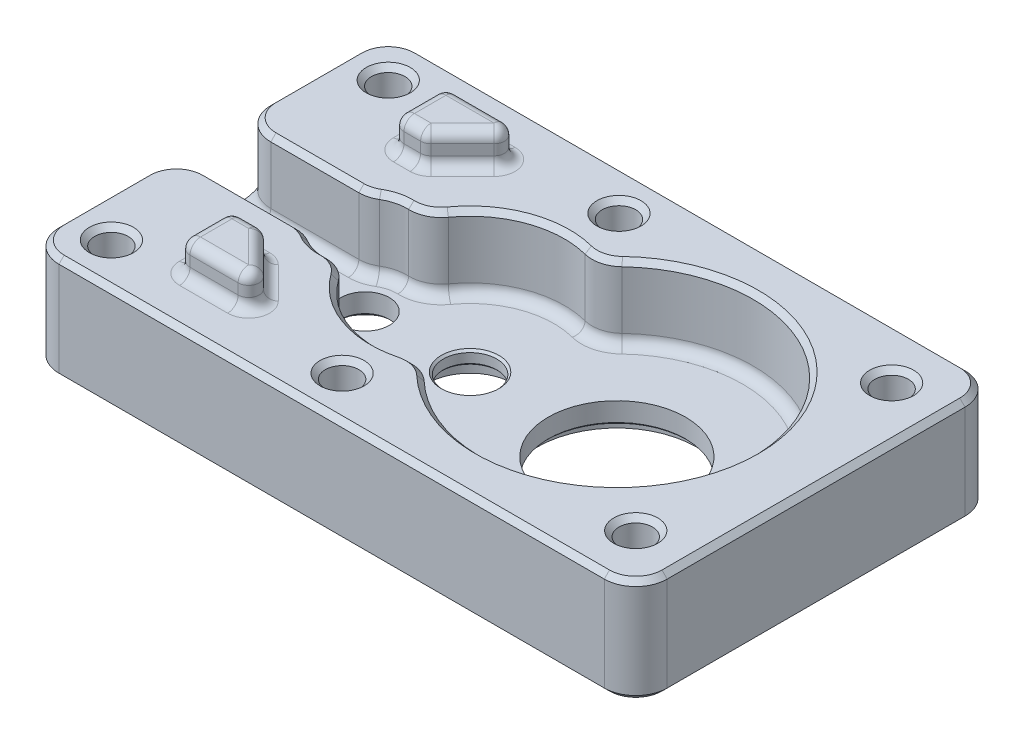
SolidWorks part; units mm, degrees
ref_plane "Front Plane" through (0, 0, 0) normal (0, 0, 1) x (1, 0, 0)
ref_plane "Top Plane" through (0, 0, 0) normal (0, 1, 0) x (1, 0, 0)
ref_plane "Right Plane" through (0, 0, 0) normal (1, 0, 0) x (0, 0, -1)
sketch "Sketch1" plane through (0, 28, 0) normal (0, 1, 0) x (1, 0, 0)
  line L1 (43, -17.2) -> (-15, -17.2)
  line L2 (43, -17.2) -> (43, 17.2)
  line L3 (43, 17.2) -> (-15, 17.2)
  line L4 (-15, -17.2) -> (-15, 17.2)
  circle A0 centre (0, 0) radius 14 construction
  circle A1 centre (0, 0) radius 2.5 construction
  circle A2 centre (10, 0) radius 7.5 construction
  circle A3 centre (10, 0) radius 2.5 construction
  circle A4 centre (24, 0) radius 11.5 construction
  circle A5 centre (24, 0) radius 3 construction
  circle A6 centre (24, 0) radius 6.5 construction
  point P4 (-15, 0)
  dimension "D4" = 28
  dimension "D5" = 5
  dimension "D6" = 15
  dimension "D7" = 5
  dimension "D8" = 23
  dimension "D9" = 6
  dimension "D10" = 13
  dimension "D1" = 34.4
  dimension "D2" = 58
  dimension "D3" = 15
extrude "Boss-Extrude1" add sketch "Sketch1" along normal blind 3 contours L4 L3 L2 L1
sketch "Sketch2" plane through (0, 28, 0) normal (0, -1, 0) x (1, 0, 0)
  circle A0 centre (0, 0) radius 3.85
  dimension "D1" = 7.7
extrude "Cut-Extrude1" cut sketch "Sketch2" against normal blind 1
sketch "Sketch3" plane through (0, 29, 0) normal (0, -1, 0) x (1, 0, 0)
  circle A0 centre (0, 0) radius 2.3
  dimension "D1" = 4.6
extrude "Cut-Extrude2" cut sketch "Sketch3" against normal through all
sketch "Sketch4" plane through (0, 31, 0) normal (0, 1, 0) x (1, 0, 0)
  line L4 (-15, -17.2) -> (43, -17.2)
  line L5 (43, -17.2) -> (43, 17.2)
  line L6 (43, 17.2) -> (-15, 17.2)
  line L7 (-15, 17.2) -> (-15, -17.2)
  line L8 (-15, -17.2) -> (43, -17.2)
  line L9 (43, -17.2) -> (43, 17.2)
  line L10 (43, 17.2) -> (-15, 17.2)
  line L11 (-15, 17.2) -> (-15, -17.2)
  arc A0 (1.75, 3.5969) -> (1.75, -3.5969) centre (0, 0) ccw
  arc A1 (1.75, -3.5969) -> (13.8571, -8.1316) centre (10, 0) ccw
  arc A2 (13.8571, -8.1316) -> (13.8571, 8.1316) centre (24, 0) ccw
  arc A3 (13.8571, 8.1316) -> (1.75, 3.5969) centre (10, 0) ccw
  dimension "D1" = 8
  dimension "D2" = 18
  dimension "D3" = 26
  dimension "D4" = 0
extrude "Boss-Extrude2" add sketch "Sketch4" along normal blind 7
sketch "Sketch5" plane through (0, 38, 0) normal (0, 1, 0) x (1, 0, 0)
  line L0 (-2.6458, 3) -> (-2.6458, -3)
  line L1 (-2.6458, 3) -> (-15, 3)
  line L2 (-2.6458, -3) -> (-15, -3)
  line L3 (-15, 3) -> (-15, -3)
  line L4 (-15, -17.2) -> (-15, 17.2) construction
  arc A0 (1.75, 3.5969) -> (1.75, -3.5969) centre (0, 0) ccw construction
  dimension "D1" = 6
extrude "Cut-Extrude3" cut sketch "Sketch5" against normal blind 7
sketch "Sketch6" plane through (0, 28, 0) normal (0, -1, 0) x (1, 0, 0)
  circle A0 centre (10, 0) radius 4.1
  dimension "D1" = 8.2
extrude "Cut-Extrude4" cut sketch "Sketch6" against normal blind 1.7
sketch "Sketch7" plane through (0, 29.7, 0) normal (0, -1, 0) x (1, 0, 0)
  circle A0 centre (10, 0) radius 2.55
  circle A1 centre (10, 0) radius 4.1 construction
  dimension "D1" = 5.1
extrude "Cut-Extrude5" cut sketch "Sketch7" against normal through all
sketch "Sketch8" plane through (0, 28, 0) normal (0, -1, 0) x (1, 0, 0)
  circle A0 centre (24, 0) radius 7.6
  dimension "D1" = 15.2
extrude "Cut-Extrude6" cut sketch "Sketch8" against normal blind 1
sketch "Sketch9" plane through (0, 29, 0) normal (0, -1, 0) x (1, 0, 0)
  circle A0 centre (24, 0) radius 6.55
  dimension "D1" = 13.1
extrude "Cut-Extrude7" cut sketch "Sketch9" against normal through all
fillet "Fillet1" radius 3 4 edges at (-15, 33, 17.2) (43, 33, 17.2) (43, 33, -17.2) (-15, 33, -17.2)
fillet "Fillet2" radius 3 8 edges at (13.8571, 34.5, 8.1316) (1.75, 34.5, 3.5969) (-2.6458, 34.5, 3) (-2.6458, 34.5, -3) (13.8571, 34.5, -8.1316) (1.75, 34.5, -3.5969) (-15, 34.5, 3) (-15, 34.5, -3)
fillet "Fillet3" radius 1 15 edges at (-14.1213, 31, 3.8787) (-7.8028, 31, 3) (-2.8038, 31, 3.1091) (-1, 31, 3.873) (1.572, 31, 4.3025) (6.9319, 31, 8.4609) (13.75, 31, 8.7142) (37, 31, 0) (13.75, 31, -8.7142) (6.9319, 31, -8.4609) (1.572, 31, -4.3025) (-1, 31, -3.873) (-2.8038, 31, -3.1091) (-14.1213, 31, -3.8787) (-7.8028, 31, -3)
chamfer "Chamfer1" distance 0.2 angle 45 4 edges at (10, 31, -2.55) (10, 29.7, -2.55) (0, 29, -2.3) (24, 29, -6.55)
sketch "Sketch10" plane through (0, 28, 0) normal (0, -1, 0) x (1, 0, 0)
  circle A0 centre (-11, -13.2) radius 1.6
  circle A1 centre (-11, -13.2) radius 2.1 construction
  circle A2 centre (11, -13.2) radius 1.6
  circle A3 centre (-11, 13.2) radius 1.6
  circle A4 centre (11, 13.2) radius 1.6
  circle A5 centre (11, 13.2) radius 2.1 construction
  dimension "D1" = 3.2
extrude "Cut-Extrude8" cut sketch "Sketch10" against normal through all
sketch "Sketch11" plane through (0, 28, 0) normal (0, -1, 0) x (1, 0, 0)
  line L0 (40, -17.2) -> (-12, -17.2) construction
  line L1 (43, 14.2) -> (43, -14.2) construction
  circle A0 centre (38, -12.2) radius 1.6
  dimension "D1" = 3.2
  dimension "D2" = 5
  dimension "D3" = 5
extrude "Cut-Extrude9" cut sketch "Sketch11" against normal through all
sketch "Sketch12" plane through (0, 28, 0) normal (0, -1, 0) x (1, 0, 0)
  circle A0 centre (38, -12.2) radius 2.1
  dimension "D1" = 4.2
extrude "Cut-Extrude10" cut sketch "Sketch12" against normal blind 5
mirror "Mirror1" about plane through (0, 0, 0) normal (0, 0, 1) of "Cut-Extrude10", "Cut-Extrude9"
sketch "Sketch13" plane through (0, 38, 0) normal (0, 1, 0) x (1, 0, 0)
  line L0 (3, -12.7) -> (-5, -12.7)
  line L1 (-5, -12.7) -> (-5, -7.7)
  line L2 (-5, -7.7) -> (-2, -7.7)
  line L3 (-2, -7.7) -> (3, -12.7)
  line L4 (-12, -17.2) -> (40, -17.2) construction
  line L5 (-15, -6) -> (-15, -14.2) construction
  dimension "D1" = 45
  dimension "D2" = 4.5
  dimension "D3" = 10
  dimension "D4" = 8
  dimension "D5" = 5
extrude "Boss-Extrude3" add sketch "Sketch13" along normal blind 3
fillet "Fillet4" radius 1 8 edges at (-1, 41, 12.7) (-5, 41, 10.2) (-3.5, 41, 7.7) (0.5, 41, 10.2) (-2, 39.5, 7.7) (-5, 39.5, 7.7) (-5, 39.5, 12.7) (3, 39.5, 12.7)
fillet "Fillet5" radius 1 8 edges at (-4.7071, 38, 12.4071) (-5, 38, 10.2) (-4.7071, 38, 7.9929) (-3.2071, 38, 7.7) (-2.0315, 38, 7.7761) (-0.2071, 38, 9.4929) (1.5097, 38, 12.0827) (-1.7071, 38, 12.7)
mirror "Mirror2" about plane through (0, 0, 0) normal (0, 0, 1) of "Fillet5", "Fillet4", "Boss-Extrude3"
chamfer "Chamfer2" distance 0.5 angle 45 44 edges at (38, 28, 14.3) (38, 28, -14.3) (-11, 28, 11.6) (11, 28, 11.6) (11, 28, -14.8) (-11, 28, -14.8) (14, 28, 17.2) (42.1213, 28, 16.3213) (-14.1213, 28, 16.3213) (43, 28, 0) (-15, 28, 0) (42.1213, 28, -16.3213) (-14.1213, 28, -16.3213) (14, 28, -17.2) (-11, 38, 11.6) (11, 38, 11.6) (38, 38, 13.8) (38, 38, -13.8) (11, 38, -14.8) (-11, 38, -14.8) (-7.8028, 38, 3) (-2.8038, 38, 3.1091) (-14.1213, 38, 3.8787) (-1, 38, 3.873) (-15, 38, 10.1) (1.572, 38, 4.3025) (-14.1213, 38, 16.3213) (6.9319, 38, 8.4609) (14, 38, 17.2) (13.75, 38, 8.7142) (42.1213, 38, 16.3213) (37, 38, 0) (43, 38, 0) (13.75, 38, -8.7142) (42.1213, 38, -16.3213) (6.9319, 38, -8.4609) (14, 38, -17.2) (1.572, 38, -4.3025) (-14.1213, 38, -16.3213) (-1, 38, -3.873) (-15, 38, -10.1) (-2.8038, 38, -3.1091) (-14.1213, 38, -3.8787) (-7.8028, 38, -3)
